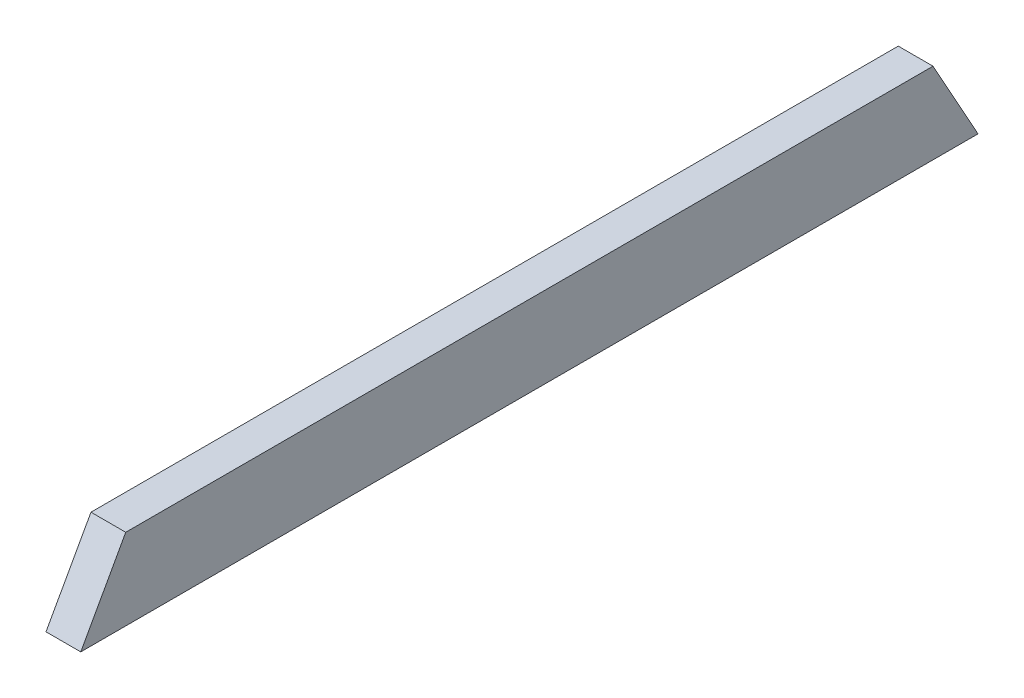
SolidWorks part; units mm, degrees
ref_plane "Front Plane" through (0, 0, 0) normal (0, 0, 1) x (1, 0, 0)
ref_plane "Top Plane" through (0, 0, 0) normal (0, 1, 0) x (1, 0, 0)
ref_plane "Right Plane" through (0, 0, 0) normal (1, 0, 0) x (0, 0, -1)
sketch "Sketch1" plane through (0, 0, 0) normal (0, 0, 1) x (1, 0, 0)
  line L1 (0, 0) -> (38.1, 0)
  line L2 (0, 0) -> (0, 88.9)
  line L3 (0, 88.9) -> (38.1, 88.9)
  line L4 (38.1, 0) -> (38.1, 88.9)
  dimension "D1" = 88.9
  dimension "D2" = 38.1
extrude "Boss-Extrude1" add sketch "Sketch1" along normal blind 983.234
sketch "Sketch2" plane through (38.1, 0, 0) normal (1, 0, 0) x (0, 0, -1)
  line L0 (-983.234, 0) -> (-933.9559, 88.9)
  line L1 (-983.234, 88.9) -> (0, 88.9) construction
  line L2 (-933.9559, 88.9) -> (-983.234, 88.9)
  line L3 (-983.234, 88.9) -> (-983.234, 0)
  line L4 (0, 0) -> (-49.2781, 88.9)
  line L5 (-49.2781, 88.9) -> (0, 88.9)
  line L6 (0, 88.9) -> (0, 0)
  dimension "D1" = 61
  dimension "D2" = 61
extrude "Cut-Extrude1" cut sketch "Sketch2" against normal through all
